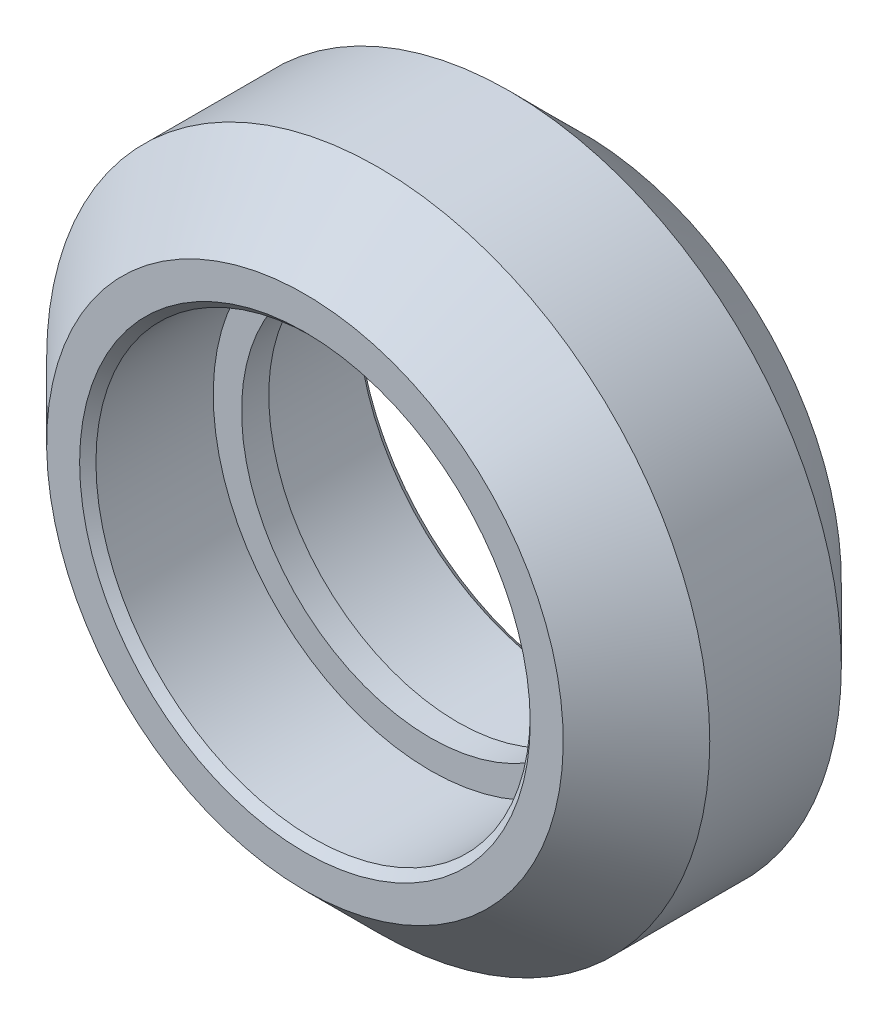
SolidWorks part; units mm, degrees
material "PC High Viscosity"
ref_plane "Front Plane" through (0, 0, 0) normal (0, 0, 1) x (1, 0, 0)
ref_plane "Top Plane" through (0, 0, 0) normal (0, 1, 0) x (1, 0, 0)
ref_plane "Right Plane" through (0, 0, 0) normal (1, 0, 0) x (0, 0, -1)
sketch "Sketch1" plane through (0, 0, 0) normal (1, 0, 0) x (0, 0, -1)
  line L0 (-5.115, 0) -> (5.115, 0) construction
  line L1 (-5.115, 12.195) -> (5.115, 12.195) construction
  line L2 (0, 12.195) -> (0, 0) construction
  line L3 (-5.115, 7.987) -> (5.115, 7.987) construction
  line L4 (-5.115, 9.5) -> (5.115, 9.5) construction
  line L5 (0, 12.195) -> (0, 15.716) construction
  line L6 (-0.5, 6.945) -> (0.5, 6.945) construction
  line L7 (-0.275, 9.375) -> (0.275, 9.375) construction
  line L8 (-2.7, 12.5215) -> (-2.7, 12.195) construction
  line L9 (-2.42, 12.195) -> (2.42, 12.195)
  line L10 (-2.42, 12.195) -> (-5.115, 9.5)
  line L11 (-5.115, 9.5) -> (-5.115, 7.987)
  line L12 (-5.115, 7.987) -> (-0.5, 7.987)
  line L13 (-0.5, 7.987) -> (-0.5, 6.945)
  line L14 (-0.5, 6.945) -> (0.5, 6.945)
  line L15 (-1.87, 12.195) -> (-0.275, 9.5) construction
  line L16 (-0.275, 9.5) -> (-0.275, 9.375) construction
  line L17 (-0.275, 9.375) -> (0.275, 9.375) construction
  line L18 (2.7, 12.5215) -> (2.7, 12.195) construction
  line L19 (0.275, 9.5) -> (0.275, 9.375) construction
  line L20 (1.87, 12.195) -> (0.275, 9.5) construction
  line L21 (0.5, 7.987) -> (0.5, 6.945)
  line L22 (5.115, 7.987) -> (0.5, 7.987)
  line L23 (5.115, 9.5) -> (5.115, 7.987)
  line L24 (2.42, 12.195) -> (5.115, 9.5)
  point P3 (0, 0)
  point P15 (0, 6.945)
  point P18 (0, 9.375)
  point P30 (0, 9.375)
  point P32 (0, 6.945)
  dimension "D1" = 10.23
  dimension "D2" = 12.195
  dimension "D3" = 7.987
  dimension "D4" = 9.5
  dimension "D5" = 6.945
  dimension "D6" = 1
  dimension "D7" = 9.375
  dimension "D8" = 0.55
  dimension "D9" = 2.7
  dimension "D10" = 0.55
  dimension "D11" = 45
ref_axis "Axis1" through (0, 0, 5.115) along (0, 0, -1)
revolve "Revolve1" add sketch "Sketch1" angle 360 about L0
chamfer "Chamfer1" distance 0.3 angle 45 2 edges at (0, -7.987, 5.115) (0, -7.987, -5.115)
